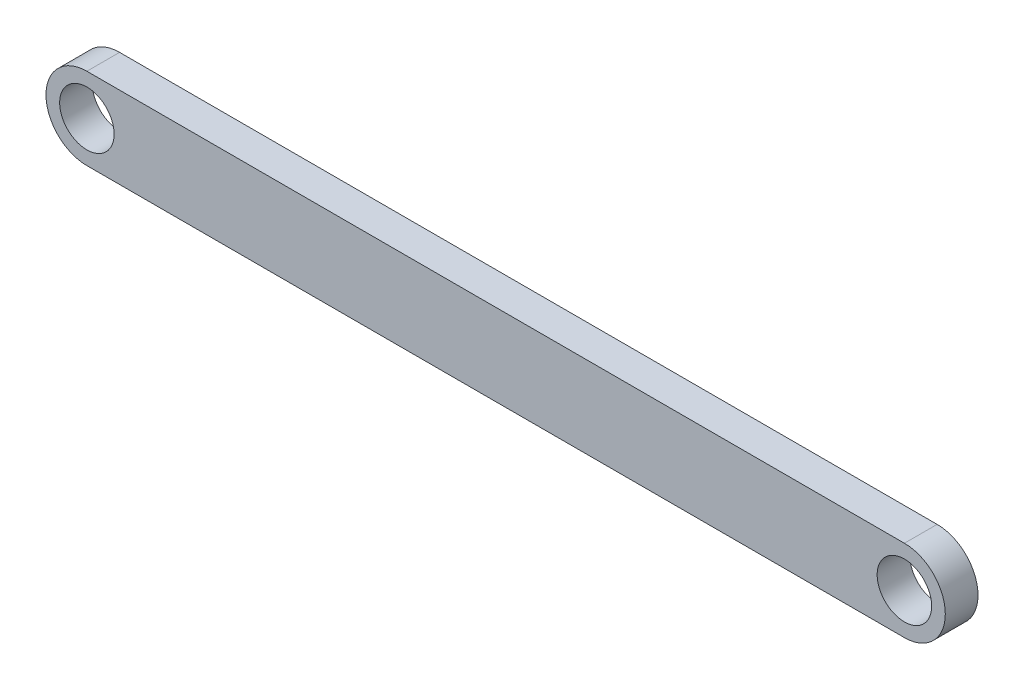
SolidWorks part; units mm, degrees
ref_plane "Front Plane" through (0, 0, 0) normal (0, 0, 1) x (1, 0, 0)
ref_plane "Top Plane" through (0, 0, 0) normal (0, 1, 0) x (1, 0, 0)
ref_plane "Right Plane" through (0, 0, 0) normal (1, 0, 0) x (0, 0, -1)
sketch "Sketch1" plane through (0, 0, 0) normal (0, 0, 1) x (1, 0, 0)
  line L0 (75, 0) -> (-75, 0) construction
  line L1 (75, -7.5) -> (-75, -7.5)
  line L2 (75, 7.5) -> (-75, 7.5)
  line L3 (0, 7.5) -> (0, -7.5) construction
  arc A0 (75, -7.5) -> (75, 7.5) centre (75, 0) ccw
  arc A1 (-75, 7.5) -> (-75, -7.5) centre (-75, 0) ccw
  circle A2 centre (75, 0) radius 5
  circle A3 centre (-75, 0) radius 5
  point P2 (0, 0)
  point P14 (19, 0)
  point P15 (-14, 0)
  point P16 (0, 3.5)
  point P17 (0, -3.5)
  point P30 (0, 3.5)
  point P33 (0, -3.5)
  dimension "D2" = 10
  dimension "D1" = 150
  dimension "D3" = 15
  dimension "D4" = 19
  dimension "D5" = 14
  dimension "D6" = 3.5
  dimension "D7" = 3.5
extrude "Boss-Extrude1" add sketch "Sketch1" along normal blind 6
